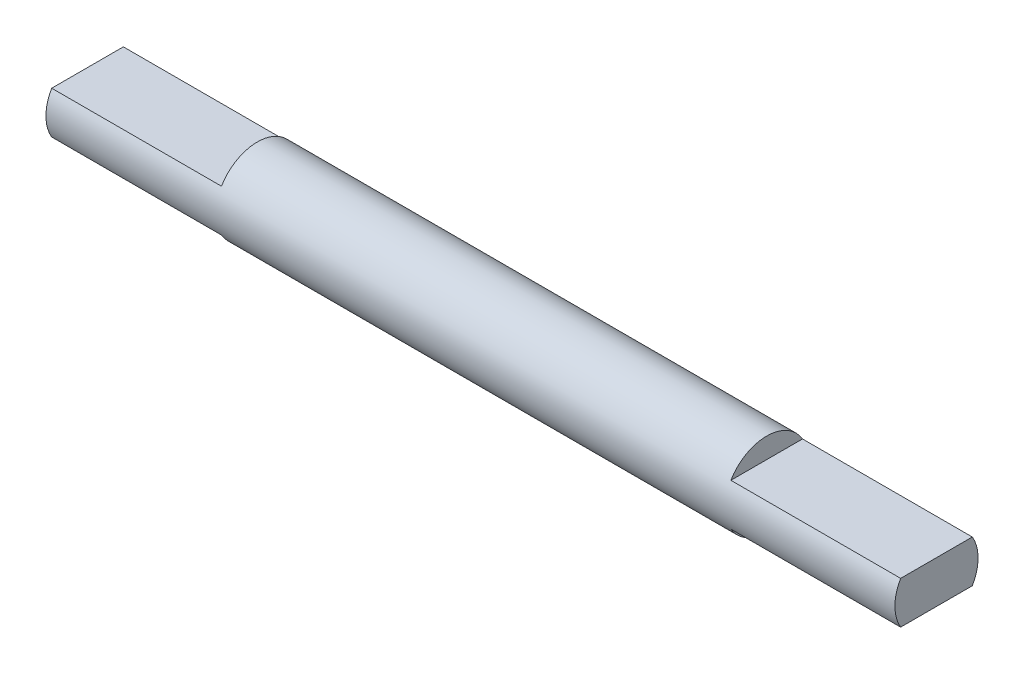
SolidWorks part; units mm, degrees
ref_plane "Front Plane" through (0, 0, 0) normal (0, 0, 1) x (1, 0, 0)
ref_plane "Top Plane" through (0, 0, 0) normal (0, 1, 0) x (1, 0, 0)
ref_plane "Right Plane" through (0, 0, 0) normal (1, 0, 0) x (0, 0, -1)
sketch "Sketch1" plane through (0, 0, 0) normal (1, 0, 0) x (0, 0, -1)
  line L0 (-2.45, 0) -> (2.45, 0) construction
  circle A0 centre (0, 0) radius 2.45
  dimension "D1" = 4.9
extrude "Boss-Extrude1" add sketch "Sketch1" along normal blind 50
sketch "Sketch2" plane through (50, 0, 0) normal (1, 0, 0) x (0, 0, -1)
  line L0 (-2.45, 0) -> (2.45, 0) construction
  line L1 (0, 1.245) -> (0, -1.245) construction
  line L2 (-2.1101, 1.245) -> (2.1101, 1.245)
  line L3 (-2.1101, -1.245) -> (2.1101, -1.245)
  arc A1 (-2.1101, 1.245) -> (2.1101, 1.245) centre (0, 0) cw
  arc A2 (-2.1101, -1.245) -> (2.1101, -1.245) centre (0, 0) ccw
  circle A3 centre (0, 0) radius 2.45 construction
  point P0 (0, -1.4585)
  point P3 (0, 0)
  point P8 (0, 0)
  point P16 (0, -1.245)
  point P17 (0, -2.45)
  dimension "D1" = 2.49
extrude "Cut-Extrude1" cut sketch "Sketch2" against normal blind 10
extrude "Cut-Extrude2" cut sketch "Sketch2<2>" along normal blind 10 from surface starting at face at (0, 0, -2.45)
sketch "Sketch2<2>" plane through (50, 0, 0) normal (1, 0, 0) x (0, 0, -1) same geometry as "Sketch2"
